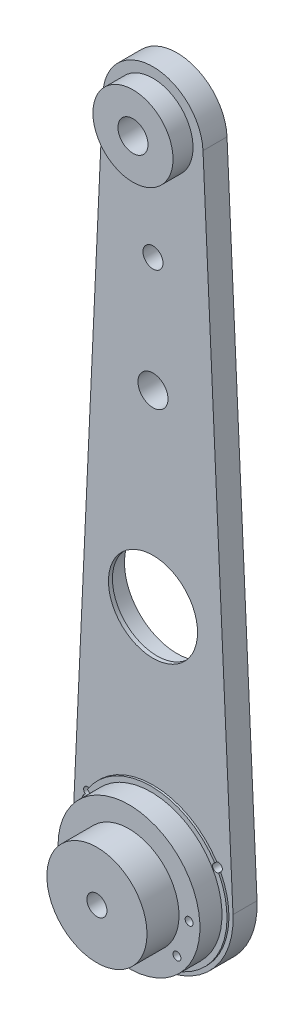
SolidWorks part; units mm, degrees
ref_plane "Front Plane" through (0, 0, 0) normal (0, 0, 1) x (1, 0, 0)
ref_plane "Top Plane" through (0, 0, 0) normal (0, 1, 0) x (1, 0, 0)
ref_plane "Right Plane" through (0, 0, 0) normal (1, 0, 0) x (0, 0, -1)
sketch "Sketch1" plane through (0, 0, 0) normal (0, 0, 1) x (1, 0, 0)
  line L0 (0, 205.4835) -> (0, 0) construction
  line L1 (25.3727, 1.1774) -> (15.8579, 206.2193)
  line L2 (-15.8579, 206.2193) -> (-25.3727, 1.1774)
  circle A1 centre (0, 205.4835) radius 4.7625
  arc A2 (-15.8579, 206.2193) -> (15.8579, 206.2193) centre (0, 205.4835) cw
  arc A3 (-25.3727, 1.1774) -> (25.3727, 1.1774) centre (0, 0) ccw
  dimension "D2" = 15.875
  dimension "D3" = 25.4
  dimension "D4" = 9.525
  dimension "D1" = 205.4835
extrude "Boss-Extrude1" add sketch "Sketch1" along normal mid plane 7.62
sketch "Sketch2" plane through (0, 0, 3.81) normal (0, 0, 1) x (1, 0, 0)
  circle A0 centre (0, 0) radius 22.5
  dimension "D1" = 45
extrude "Boss-Extrude2" add sketch "Sketch2" along normal blind 7.62
sketch "Sketch3" plane through (0, 0, 3.81) normal (0, 0, 1) x (1, 0, 0)
  circle A0 centre (0, 0) radius 24.0899
extrude "Boss-Extrude3" add sketch "Sketch3" along normal offset from surface (0.62 mm away) 7 up to face at (22.5, 0, 11.43)
sketch "Sketch4" plane through (0, 0, 3.81) normal (0, 0, 1) x (1, 0, 0)
  circle A0 centre (0, 73.0199) radius 16.6687
  circle A1 centre (0, 132.4635) radius 4.7625
  circle A2 centre (0, 205.4835) radius 4.7625 construction
  dimension "D2" = 33.3375
  dimension "D3" = 9.525
  dimension "D1" = 73.0199
  dimension "D4" = 73.0199
extrude "Cut-Extrude1" cut sketch "Sketch4" against normal through all both and the other way through all
sketch "Sketch6" plane through (0, 0, 3.81) normal (0, 0, 1) x (1, 0, 0)
  circle A0 centre (0, 73.0199) radius 16.6687
  circle A1 centre (0, 73.0199) radius 14.1287
  circle A2 centre (0, 73.0199) radius 16.6687 construction
  dimension "D1" = 2.54
extrude "Boss-Extrude4" add sketch "Sketch6" against normal offset from surface (1.27 mm away) 6.35 up to face at (16.6687, 73.0199, -3.81)
sketch "Sketch5" plane through (0, 0, 0) normal (0, 0, 1) x (1, 0, 0)
  line L0 (-155.5635, 72.3706) -> (0, 227.9341)
  line L1 (-155.5635, 72.3706) -> (0, -83.1929)
  line L2 (0, 227.9341) -> (155.5635, 72.3706)
  line L3 (0, -83.1929) -> (155.5635, 72.3706)
  line L4 (-155.5635, 72.3706) -> (155.5635, 72.3706) construction
  line L5 (0, 227.9341) -> (0, -83.1929) construction
  arc A1 (15.8579, 206.2193) -> (-15.8579, 206.2193) centre (0, 205.4835) ccw construction
  point P1 (0, 72.3706)
  dimension "D1" = 220
sketch "Sketch7" plane through (0, 0, -3.81) normal (0, 0, -1) x (-1, 0, 0)
  line L1 (-11.7937, -8.3562) -> (-11.7937, 8.3562)
  line L2 (11.7937, -8.3562) -> (11.7937, 8.3562)
  line L3 (-11.7937, 8.3562) -> (11.7937, 8.3562)
  line L4 (-11.7937, -8.3562) -> (11.7937, 8.3562) construction
  line L5 (11.7937, -8.3562) -> (-11.7937, 8.3562) construction
  line L6 (-11, 7.5625) -> (-11.7937, 8.3562) construction
  line L7 (11.7937, 8.3562) -> (11, 7.5625) construction
  line L8 (-11.7937, -8.3562) -> (-11.7937, -22.4959)
  line L10 (11.7937, -22.4959) -> (11.7937, -8.3562)
  line L11 (-11, 7.5625) -> (-11, -20.6542) construction
  arc A0 (-11.7937, -22.4959) -> (11.7937, -22.4959) centre (0, 0) ccw
  arc A1 (-25.3727, 1.1774) -> (25.3727, 1.1774) centre (0, 0) ccw construction
  point P0 (11, 7.5625)
  point P1 (0, 0)
  point P2 (-11, 7.5625)
  point P11 (11, -20.6542)
  dimension "D1" = 0.7937
extrude "Cut-Extrude2" cut sketch "Sketch7" against normal blind 1.5875
sketch "Sketch8" plane through (0, 0, -2.2225) normal (0, 0, -1) x (-1, 0, 0)
  circle A0 centre (9, -5.5625) radius 0.95
  circle A1 centre (-9, -5.5625) radius 0.95
  circle A2 centre (-9, 5.5625) radius 0.95
  circle A3 centre (9, 5.5625) radius 0.95
  dimension "D1" = 1.9
extrude "Cut-Extrude3" cut sketch "Sketch8" against normal through all
sketch "Sketch9" plane through (0, 0, 3.81) normal (0, 0, 1) x (1, 0, 0)
  circle A0 centre (0, 205.4835) radius 12.7
  circle A1 centre (0, 205.4835) radius 4.7625 construction
  circle A2 centre (0, 205.4835) radius 4.7625
  dimension "D1" = 25.4
extrude "Boss-Extrude5" add sketch "Sketch9" along normal blind 6.35
sketch "Sketch10" plane through (0, 0, 11.43) normal (0, 0, 1) x (1, 0, 0)
  circle A0 centre (0, 0) radius 15.875
  dimension "D1" = 31.75
extrude "Boss-Extrude6" add sketch "Sketch10" along normal blind 10.16
sketch "Sketch11" plane through (0, 0, -3.81) normal (0, 0, -1) x (-1, 0, 0)
  circle A0 centre (-20.7431, 11.983) radius 1.25
  circle A1 centre (-19.0618, 0) radius 1.25
  circle A2 centre (-15.2212, -11.4747) radius 1.25
  circle A3 centre (15.2212, -11.4747) radius 1.25
  circle A4 centre (19.0618, 0) radius 1.25
  circle A5 centre (20.7431, 11.983) radius 1.25
  dimension "D1" = 2.5
extrude "Cut-Extrude4" cut sketch "Sketch11" against normal through all both and the other way through all
sketch "Sketch12" plane through (0, 0, 3.81) normal (0, 0, 1) x (1, 0, 0)
  line L0 (0, 205.4835) -> (0, 132.4635) construction
  circle A8 centre (0, 168.9735) radius 3.175
  dimension "D1" = 6.35
extrude "Cut-Extrude5" cut sketch "Sketch12" against normal through all both and the other way through all
sketch "Sketch14" plane through (0, 0, -2.2225) normal (0, 0, -1) x (-1, 0, 0)
  circle A0 centre (0, 0) radius 3.175
  dimension "D1" = 6.35
extrude "Cut-Extrude6" cut sketch "Sketch14" against normal through all
sketch "Sketch15" plane through (0, 0, -2.2225) normal (0, 0, -1) x (-1, 0, 0)
  circle A0 centre (0, 0) radius 6.35
  dimension "D1" = 12.7
extrude "Cut-Extrude7" cut sketch "Sketch15" against normal blind 7.62
equation "\"UpperLinkLength\"= \"LowerFirstStage\" + \"LowerSecondStage\""
equation "\"LowerFirstStage\"= \"60T_20T_171B\""
equation "\"LowerSecondStage\"= \"60T_20T_113B\""
equation "\"D1@Sketch1\"=\"UpperLinkLength\""
equation "\"UpperStage\"= \"60T_20T_113B\""
equation "\"60T_20T_113B\"= 2.8748"
equation "\"60T_20T_171B\"= 5.2151"
equation "\"D1@Sketch4\"=\"UpperStage\""
equation "\"D4@Sketch4\"=\"LowerSecondStage\""
